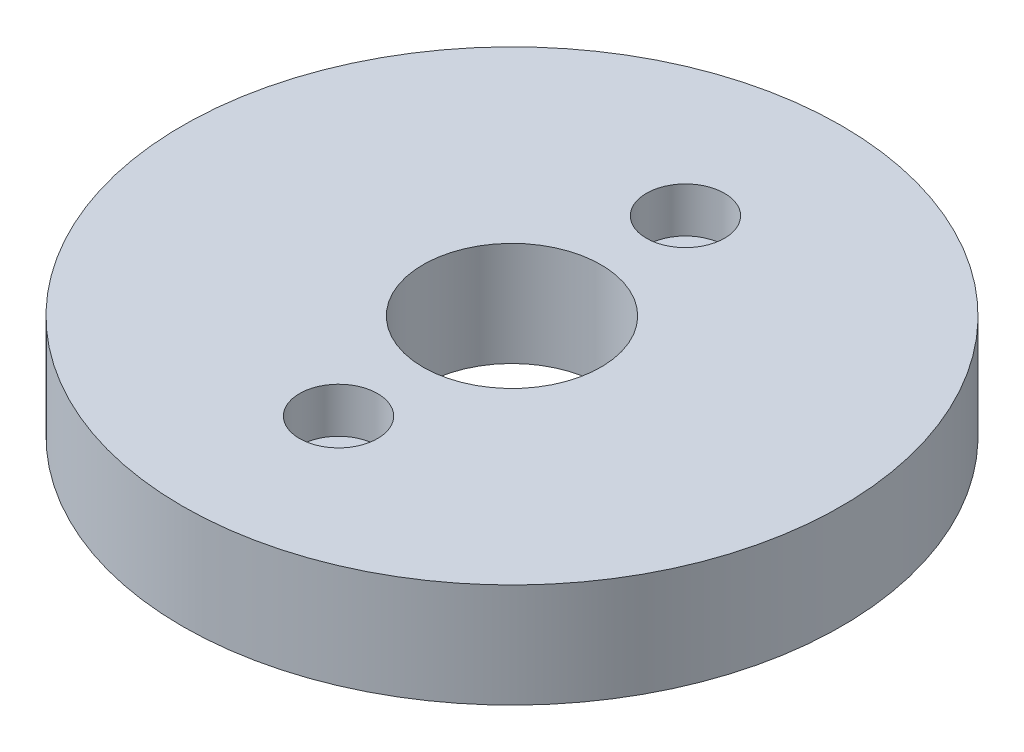
SolidWorks part; units mm, degrees
ref_plane "Front Plane" through (0, 0, 0) normal (0, 0, 1) x (1, 0, 0)
ref_plane "Top Plane" through (0, 0, 0) normal (0, 1, 0) x (1, 0, 0)
ref_plane "Right Plane" through (0, 0, 0) normal (1, 0, 0) x (0, 0, -1)
sketch "Sketch1" plane through (0, 0, 0) normal (0, 1, 0) x (1, 0, 0)
  circle A0 centre (0, 0) radius 38
extrude "Boss-Extrude1" add sketch "Sketch1" along normal blind 12
sketch "Sketch2" plane through (0, 12, 0) normal (0, 1, 0) x (1, 0, 0)
  circle A0 centre (0, 20) radius 2.75
  circle A1 centre (0, -20) radius 2.75
  dimension "D1" = 20
  dimension "D2" = 20
extrude "Cut-Extrude1" cut sketch "Sketch2" against normal blind 25
sketch "Sketch3" plane through (0, 12, 0) normal (0, 1, 0) x (1, 0, 0)
  circle A1 centre (0, 20) radius 4.5
  circle A2 centre (0, -20) radius 4.5
sketch "Sketch4" plane through (0, 12, 0) normal (0, 1, 0) x (1, 0, 0)
  circle A0 centre (0, 0) radius 10.25
extrude "Cut-Extrude2" cut sketch "Sketch4" against normal blind 25
extrude "Cut-Extrude3" cut sketch "Sketch3" against normal blind 5.2
